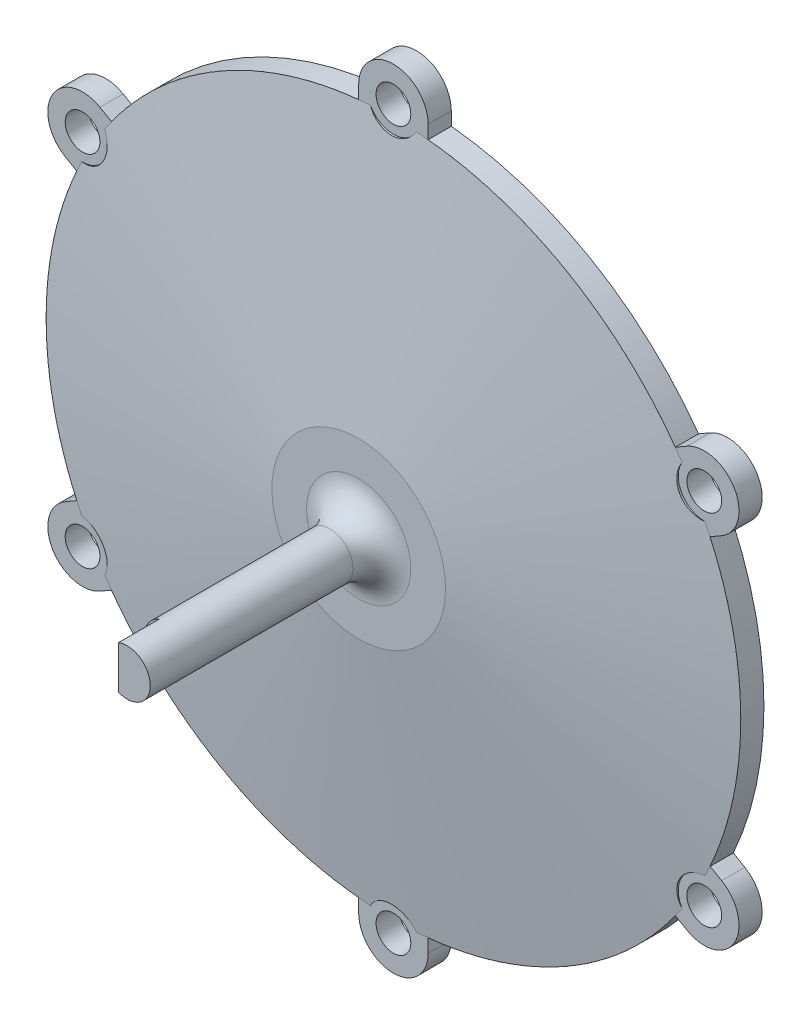
SolidWorks part; units mm, degrees
ref_plane "Front Plane" through (0, 0, 0) normal (0, 0, 1) x (1, 0, 0)
ref_plane "Top Plane" through (0, 0, 0) normal (0, 1, 0) x (1, 0, 0)
ref_plane "Right Plane" through (0, 0, 0) normal (1, 0, 0) x (0, 0, -1)
sketch "Sketch1" plane through (0, 0, 0) normal (0, 0, 1) x (1, 0, 0)
  line L0 (-6, 62) -> (-6, 59.6992)
  line L1 (6, 62) -> (6, 59.6992)
  line L2 (50.6936, 36.1962) -> (48.7011, 35.0458)
  line L3 (56.6936, 25.8038) -> (54.7011, 24.6535)
  line L4 (56.6936, -25.8038) -> (54.7011, -24.6535)
  line L5 (50.6936, -36.1962) -> (48.7011, -35.0458)
  line L6 (6, -62) -> (6, -59.6992)
  line L7 (-6, -62) -> (-6, -59.6992)
  line L8 (-50.6936, -36.1962) -> (-48.7011, -35.0458)
  line L9 (-56.6936, -25.8038) -> (-54.7011, -24.6535)
  line L10 (-56.6936, 25.8038) -> (-54.7011, 24.6535)
  line L11 (-50.6936, 36.1962) -> (-48.7011, 35.0458)
  line L12 (0, 0) -> (6, 59.6992) construction
  circle A0 centre (0, 0) radius 57
  circle A1 centre (0, 0) radius 60
  arc A2 (6, 62) -> (-6, 62) centre (0, 62) ccw
  arc A3 (56.6936, 25.8038) -> (50.6936, 36.1962) centre (53.6936, 31) ccw
  arc A4 (50.6936, -36.1962) -> (56.6936, -25.8038) centre (53.6936, -31) ccw
  arc A5 (-6, -62) -> (6, -62) centre (0, -62) ccw
  arc A6 (-56.6936, -25.8038) -> (-50.6936, -36.1962) centre (-53.6936, -31) ccw
  arc A7 (-50.6936, 36.1962) -> (-56.6936, 25.8038) centre (-53.6936, 31) ccw
  dimension "D1" = 120
  dimension "D2" = 3
  dimension "D3" = 6
  dimension "D4" = 62
  dimension "D5" = 6
extrude "Boss-Extrude1" add sketch "Sketch1" along normal blind 4 contours L11 A7 L10 A1 | L1 A2 L0 A1 | L3 A3 L2 A1 | L5 A4 L4 A1 | L7 A5 L6 A1 | L9 A6 L8 A1 | A0 A1 region at (0, 63.4372, 0) region at (0, 58.3029, 0) region at (-54.9382, 31.7186, 0) region at (54.9382, 31.7186, 0) region at (-54.9382, -31.7186, 0) region at (54.9382, -31.7186, 0) region at (0, -63.4372, 0)
sketch "Sketch3" plane through (0, 0, 0) normal (0, 1, 0) x (1, 0, 0)
  line L0 (0, -4) -> (60, -4)
  line L1 (-6, -4) -> (6, -4) construction
  line L2 (60, -4) -> (15, -10)
  line L3 (15, -10) -> (0, -10)
  line L4 (0, -10) -> (0, -4)
  line L5 (48.7011, 0) -> (6, 0) construction
  line L6 (48.7011, 0) -> (6, 0) construction
  line L7 (0, -4) -> (60, -4)
  line L8 (0, -4) -> (0, -0.5)
  line L9 (0, -0.5) -> (57, -0.5)
  line L13 (57, -0.5) -> (57, -4)
  line L15 (-57, -4) -> (57, -4) construction
  point P15 (0, 0)
  point P16 (0, 0)
  point P17 (0, 0)
  dimension "D1" = 10
  dimension "D2" = 15
  dimension "D3" = 0.5
  dimension "D4" = 3
revolve "Revolve1" add sketch "Sketch3" angle 360 about L4 region at (28.5, 0, 2.25) region at (21, 0, 6.4) other way angle 360
sketch "Sketch4" plane through (0, 0, 0.5) normal (0, 0, 1) x (1, 0, 0)
  circle A0 centre (0, 0) radius 14
  dimension "D1" = 28
extrude "Cut-Extrude1" cut sketch "Sketch4" along normal blind 7 contours A0
sketch "Sketch9" plane through (0, 0, 7.5) normal (0, 0, -1) x (-1, 0, 0)
  circle A0 centre (0, 0) radius 10.5
  dimension "D1" = 21
extrude "Cut-Extrude4" cut sketch "Sketch9" against normal blind 0.5
sketch "Sketch10" plane through (0, 0, 10) normal (0, 0, 1) x (1, 0, 0)
  circle A0 centre (0, 0) radius 4
  dimension "D1" = 8
extrude "Boss-Extrude2" add sketch "Sketch10" along normal blind 40
fillet "Fillet1" radius 5 1 edges at (4, 0, 10)
sketch "Sketch7" plane through (0, 0, 4) normal (0, 0, 1) x (1, 0, 0)
  circle A0 centre (0, 62) radius 3
  arc A1 (6, 62) -> (-6, 62) centre (0, 62) ccw construction
  dimension "D1" = 6
extrude "Cut-Extrude2" cut sketch "Sketch7" against normal through all
sketch "Sketch8" plane through (0, 0, 4) normal (0, 0, 1) x (1, 0, 0)
  circle A0 centre (0, 62) radius 4.5
  dimension "D1" = 9
extrude "Cut-Extrude3" cut sketch "Sketch8" along normal through all
pattern_circular "CirPattern6" count 6 over 360 about axis through (0, 0, 4) along (0, 0, 1) of "Cut-Extrude2", "Cut-Extrude3"
sketch "Sketch11" plane through (0, 0, 50) normal (0, 0, 1) x (1, 0, 0)
  line L1 (-1.5, 3.7081) -> (-4, 3.7081)
  line L2 (-1.5, 3.7081) -> (-1.5, -3.7081)
  line L3 (-1.5, -3.7081) -> (-4, -3.7081)
  line L4 (-4, 3.7081) -> (-4, -3.7081)
  circle A0 centre (0, 0) radius 4 construction
  point P4 (0, 0)
  point P7 (0, 0)
  dimension "D1" = 2.5
extrude "Cut-Extrude5" cut sketch "Sketch11" against normal blind 7
